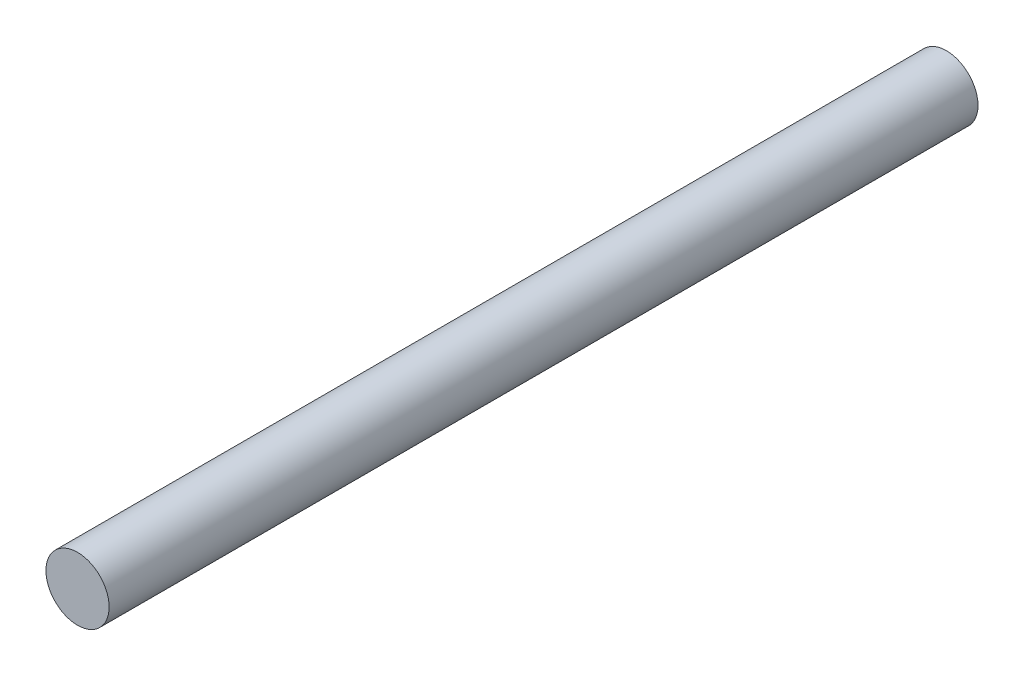
SolidWorks part; units mm, degrees
ref_plane "Front Plane" through (0, 0, 0) normal (0, 0, 1) x (1, 0, 0)
ref_plane "Top Plane" through (0, 0, 0) normal (0, 1, 0) x (1, 0, 0)
ref_plane "Right Plane" through (0, 0, 0) normal (1, 0, 0) x (0, 0, -1)
sketch "Sketch1" plane through (0, 0, 0) normal (0, 0, 1) x (1, 0, 0)
  circle A0 centre (0, 0) radius 3
extrude "Boss-Extrude1" add sketch "Sketch1" along normal blind 41.25 and the other way blind 41.25
